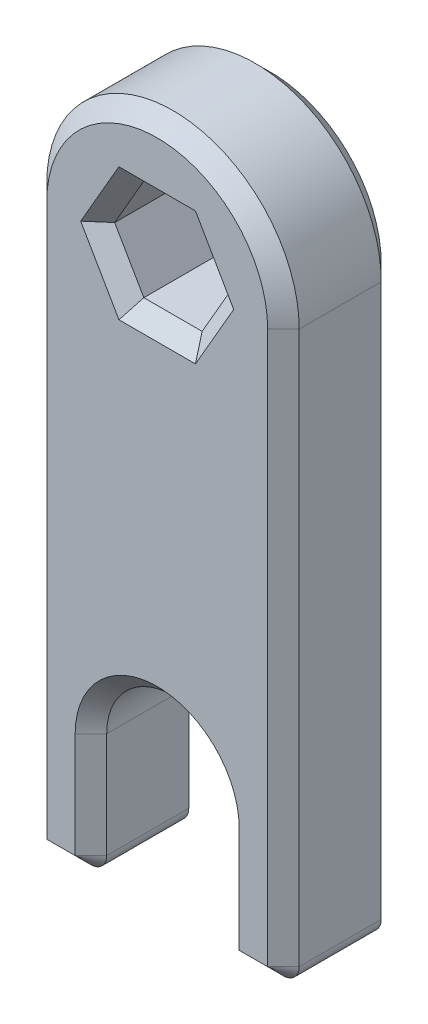
SolidWorks part; units mm, degrees
ref_plane "Front Plane" through (0, 0, 0) normal (0, 0, 1) x (1, 0, 0)
ref_plane "Top Plane" through (0, 0, 0) normal (0, 1, 0) x (1, 0, 0)
ref_plane "Right Plane" through (0, 0, 0) normal (1, 0, 0) x (0, 0, -1)
ref_plane "Plane1" through (0, 0, 0) normal (0, 0, -1) x (-1, 0, 0)
sketch "Sketch1" plane through (0, 0, 0) normal (0, 0, -1) x (-1, 0, 0)
  line L0 (-4, 14) -> (-4, 4)
  line L1 (-4, 4) -> (4, 4)
  line L2 (4, 4) -> (4, 14)
  line L19 (-0.9238, 12.4) -> (-1.8475, 14)
  line L20 (-1.8475, 14) -> (-0.9238, 15.6)
  line L21 (-0.9238, 15.6) -> (0.9238, 15.6)
  line L22 (0.9238, 15.6) -> (1.8475, 14)
  line L23 (1.8475, 14) -> (0.9238, 12.4)
  line L24 (0.9238, 12.4) -> (-0.9238, 12.4)
  arc A0 (4, 14) -> (-4, 14) centre (0, 14) ccw
extrude "Boss-Extrude1" add sketch "Sketch1" against normal blind 3.6
sketch "Sketch6" plane through (0, 0, 0) normal (0, 0, -1) x (-1, 0, 0)
  line L0 (-4, -4) -> (-2.1, -4)
  line L1 (-2.1, -4) -> (-2.1, -0.1564)
  line L8 (2.1, -0.1564) -> (2.1, -4)
  line L9 (2.1, -4) -> (4, -4)
  line L10 (4, -4) -> (4, 4)
  line L11 (4, 4) -> (-4, 4)
  line L12 (-4, 4) -> (-4, -4)
  arc A0 (2.1, -0.1564) -> (-2.1, -0.1564) centre (0, -0.1564) ccw
extrude "Boss-Extrude2" add sketch "Sketch6" against normal blind 3.6
fillet "Fillet1" radius 0.5 4 edges at (4, -4, 1.8) (2.1, -4, 1.8) (-4, -4, 1.8) (-2.1, -4, 1.8)
chamfer "Chamfer1" distance 0.5 angle 45 36 edges at (0, 18, 0) (-4, 5.25, 0) (-3.8536, -3.8536, 0) (-3.05, -4, 0) (-2.2464, -3.8536, 0) (-2.1, -1.8282, 0) (0, 1.9436, 0) (2.1, -1.8282, 0) (2.2464, -3.8536, 0) (3.05, -4, 0) (3.8536, -3.8536, 0) (4, 5.25, 0) (-1.3856, 13.2, 0) (-1.3856, 14.8, 0) (0, 15.6, 0) (1.3856, 14.8, 0) (1.3856, 13.2, 0) (0, 12.4, 0) (2.2464, -3.8536, 3.6) (2.1, -1.8282, 3.6) (0, 1.9436, 3.6) (-2.1, -1.8282, 3.6) (-2.2464, -3.8536, 3.6) (-3.05, -4, 3.6) (-3.8536, -3.8536, 3.6) (-4, 5.25, 3.6) (0, 18, 3.6) (4, 5.25, 3.6) (3.8536, -3.8536, 3.6) (3.05, -4, 3.6) (1.3856, 14.8, 3.6) (0, 15.6, 3.6) (-1.3856, 14.8, 3.6) (-1.3856, 13.2, 3.6) (0, 12.4, 3.6) (1.3856, 13.2, 3.6)
ref_plane "Plane2" through (0, 0, 1.8) normal (0, 0, -1) x (-1, 0, 0)
